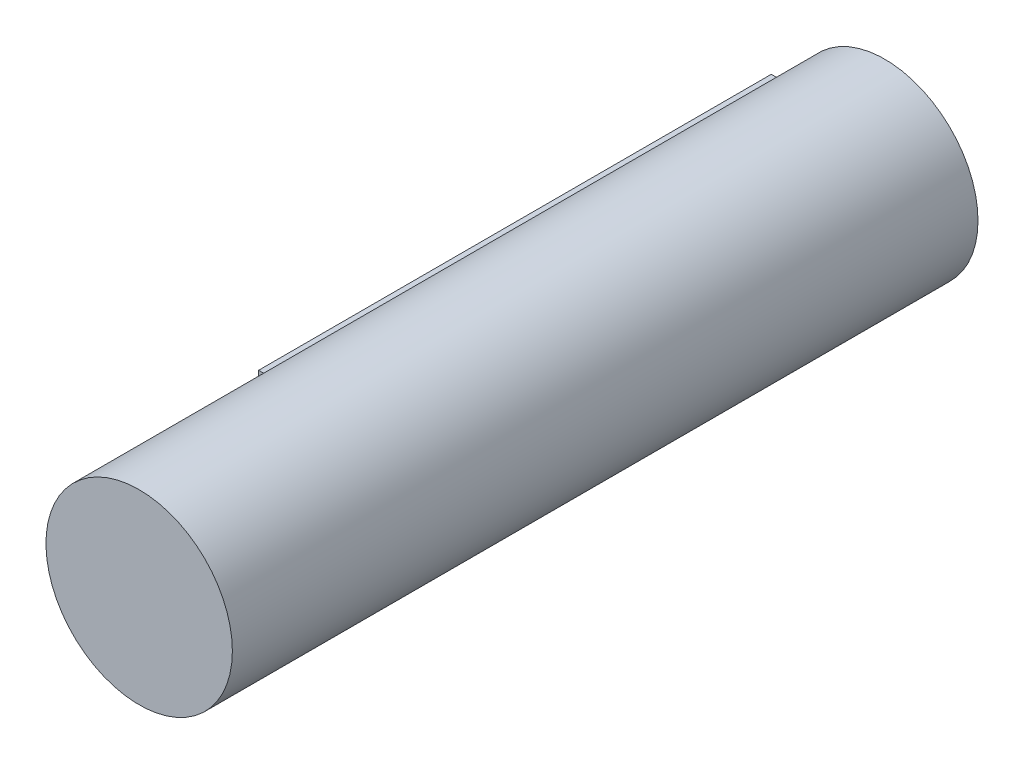
SolidWorks part; units mm, degrees
ref_plane "Front Plane" through (0, 0, 0) normal (0, 0, 1) x (1, 0, 0)
ref_plane "Top Plane" through (0, 0, 0) normal (0, 1, 0) x (1, 0, 0)
ref_plane "Right Plane" through (0, 0, 0) normal (1, 0, 0) x (0, 0, -1)
sketch "Sketch1" plane through (0, 0, 0) normal (0, 0, 1) x (1, 0, 0)
  line L0 (-38.5693, 0) -> (38.6732, 0) construction
  line L1 (-19.3649, 5) -> (-24.3649, 5)
  line L2 (-19.3649, -5) -> (-24.3649, -5)
  line L3 (-24.3649, 5) -> (-24.3649, -5)
  circle A0 centre (0, 0) radius 20
  dimension "D1" = 40
  dimension "D2" = 5
  dimension "D3" = 10
extrude "Boss-Extrude1" add sketch "Sketch1" along normal blind 160 contours L0 A0 | A0 L0 region at (0, 8.4883, 0) region at (0, -8.4883, 0)
extrude "Boss-Extrude2" add sketch "Sketch1<3>" along normal blind 110 contours L3 L0 A0 L1 | L0 L3 L2 A0 region at (-22.0734, 2.5576, 0) region at (-22.0734, -2.5576, 0)
sketch "Sketch1<3>" plane through (0, 0, 0) normal (0, 0, 1) x (1, 0, 0) same geometry as "Sketch1"
